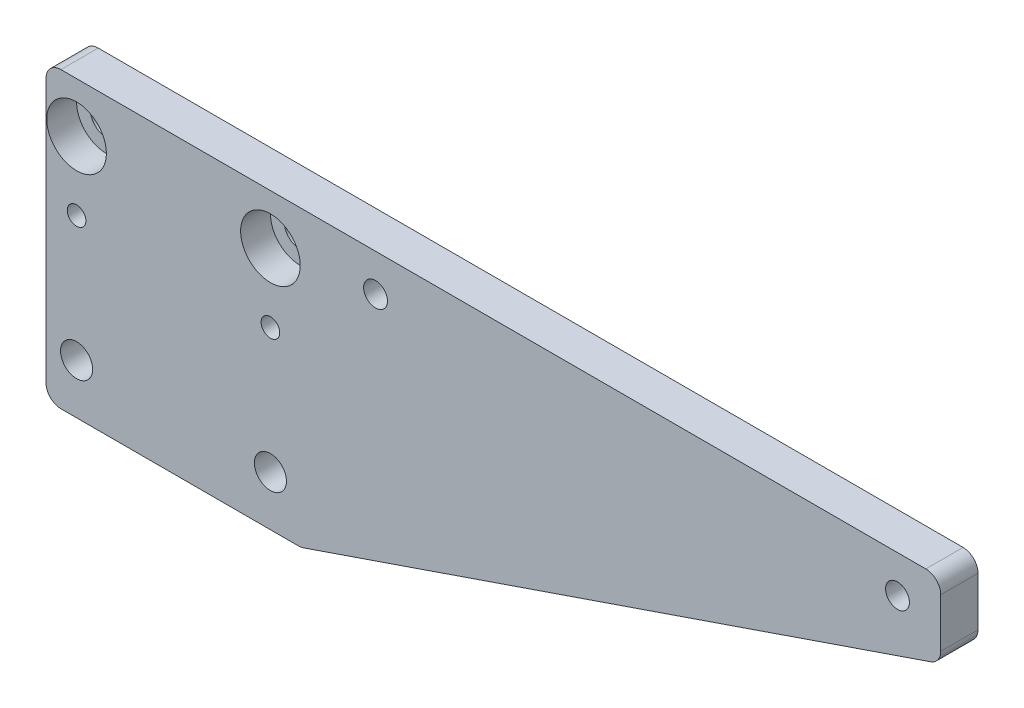
SolidWorks part; units mm, degrees
material "AISI 1045 Steel, cold drawn"
ref_plane "Front Plane" through (0, 0, 0) normal (0, 0, 1) x (1, 0, 0)
ref_plane "Top Plane" through (0, 0, 0) normal (0, 1, 0) x (1, 0, 0)
ref_plane "Right Plane" through (0, 0, 0) normal (1, 0, 0) x (0, 0, -1)
sketch "Sketch1" plane through (0, 0, 0) normal (0, 0, 1) x (1, 0, 0)
  line L0 (17.1, 19.7) -> (102.9, 19.7)
  line L1 (13, -13) -> (-13, -13) construction
  line L2 (13, -13) -> (13, 13) construction
  line L3 (13, 13) -> (-13, 13) construction
  line L4 (-13, -13) -> (-13, 13) construction
  line L5 (13, -13) -> (-13, 13) construction
  line L6 (13, 13) -> (-13, -13) construction
  line L7 (17.1, -19.7) -> (-17.1, -19.7)
  line L8 (17.1, -19.7) -> (17.1, 19.7) construction
  line L9 (17.1, 19.7) -> (-17.1, 19.7)
  line L10 (-17.1, -19.7) -> (-17.1, 19.7)
  line L11 (17.1, -19.7) -> (-17.1, 19.7) construction
  line L12 (17.1, 19.7) -> (-17.1, -19.7) construction
  line L13 (102.9, 19.7) -> (102.9, 9.7)
  line L14 (102.9, 9.7) -> (17.1, -19.7)
  point P0 (0, 0)
  point P6 (0, 0)
  dimension "D1" = 39.4
  dimension "D2" = 120
  dimension "D3" = 34.2
  dimension "D4" = 26
  dimension "D5" = 10
extrude "Boss-Extrude1" add sketch "Sketch1" along normal blind 5
hole_wizard "CBORE for M4 SHCS1" positions "Sketch2" profile "Sketch3" counterbore size "M4" standard "ANSI Metric" end condition through all
sketch "Sketch2" plane through (0, 0, 5) normal (0, 0, 1) x (1, 0, 0)
  point P0 (13, 13)
  point P3 (-13, 13)
  point P14 (0, 0)
  point P15 (0, 0)
sketch "Sketch3" plane through (13, 13, 5) normal (1, 0, 0) x (0, -1, 0)
  line L0 (0, 0) -> (0, 5)
  line L1 (0, 5) -> (2.15, 5)
  line L3 (2.15, 5) -> (2.15, 4)
  line L4 (2.15, 4) -> (4, 4)
  line L5 (4, 4) -> (4, 0)
  line L7 (4, 0) -> (0, 0)
  line L11 (0, -6.35) -> (0, 107.95) construction
  dimension "Thru Hole Dia." = 4.3
  dimension "Thru Hole Depth" = 5
  dimension "C'Bore Dia." = 8
  dimension "C'Bore Depth" = 4
hole_wizard "M4 Clearance Hole1" positions "Sketch10" profile "Sketch11" hole size "M4" standard "ANSI Metric" end condition through all
sketch "Sketch10" plane through (0, 0, 5) normal (0, 0, 1) x (1, 0, 0)
  point P0 (-13, -13)
  point P3 (13, -13)
sketch "Sketch11" plane through (-13, -13, 5) normal (1, 0, 0) x (0, -1, 0)
  line L0 (0, 0) -> (0, 5)
  line L1 (0, 5) -> (2.15, 5)
  line L2 (2.15, 5) -> (2.15, 0)
  line L5 (2.15, 0) -> (0, 0)
  line L11 (0, -6.35) -> (0, 107.95) construction
  dimension "Thru Hole Dia." = 4.3
  dimension "Thru Hole Depth" = 5
hole_wizard "Tap Drill for M3x0.5 Tap1" positions "Sketch4" profile "Sketch5" hole size "M3x0.5" standard "ANSI Metric" end condition through all
sketch "Sketch4" plane through (0, 0, 5) normal (0, 0, 1) x (1, 0, 0)
  line L0 (-13, 3.8) -> (13, 3.8) construction
  line L2 (102.9, 19.7) -> (-17.1, 19.7) construction
  point P0 (-13, 3.8)
  point P2 (13, 3.8)
  point P10 (0, 3.8)
  dimension "D1" = 15.9
  dimension "D2" = 26
sketch "Sketch5" plane through (-13, 3.8, 5) normal (1, 0, 0) x (0, -1, 0)
  line L0 (0, 0) -> (0, 5)
  line L1 (0, 5) -> (1.25, 5)
  line L2 (1.25, 5) -> (1.25, 0)
  line L5 (1.25, 0) -> (0, 0)
  line L11 (0, -6.35) -> (0, 107.95) construction
  dimension "Thru Hole Dia." = 2.5
  dimension "Thru Hole Depth" = 5
hole_wizard "M3 Clearance Hole2" positions "Sketch7" profile "Sketch9" hole size "M3" standard "ANSI Metric" end condition through all
sketch "Sketch7" plane through (0, 0, 0) normal (0, 0, -1) x (-1, 0, 0)
  line L1 (-97.1, 14.7) -> (-27.1, 14.7) construction
  line L3 (-102.9, 9.7) -> (-102.9, 19.7) construction
  point P0 (-97.1, 14.7)
  point P2 (-27.1, 14.7)
  point P21 (-102.9, 14.7)
  dimension "D1" = 10
  dimension "D2" = 70
sketch "Sketch9" plane through (97.1, 14.7, 0) normal (1, 0, 0) x (0, 1, 0)
  line L0 (0, 0) -> (0, 5)
  line L1 (0, 5) -> (1.6, 5)
  line L2 (1.6, 5) -> (1.6, 0)
  line L5 (1.6, 0) -> (0, 0)
  line L11 (0, -6.35) -> (0, 107.95) construction
  dimension "Thru Hole Dia." = 3.2
  dimension "Thru Hole Depth" = 5
fillet "Fillet1" radius 2 5 edges at (17.1, -19.7, 2.5) (-17.1, -19.7, 2.5) (102.9, 19.7, 2.5) (-17.1, 19.7, 2.5) (102.9, 9.7, 2.5)
